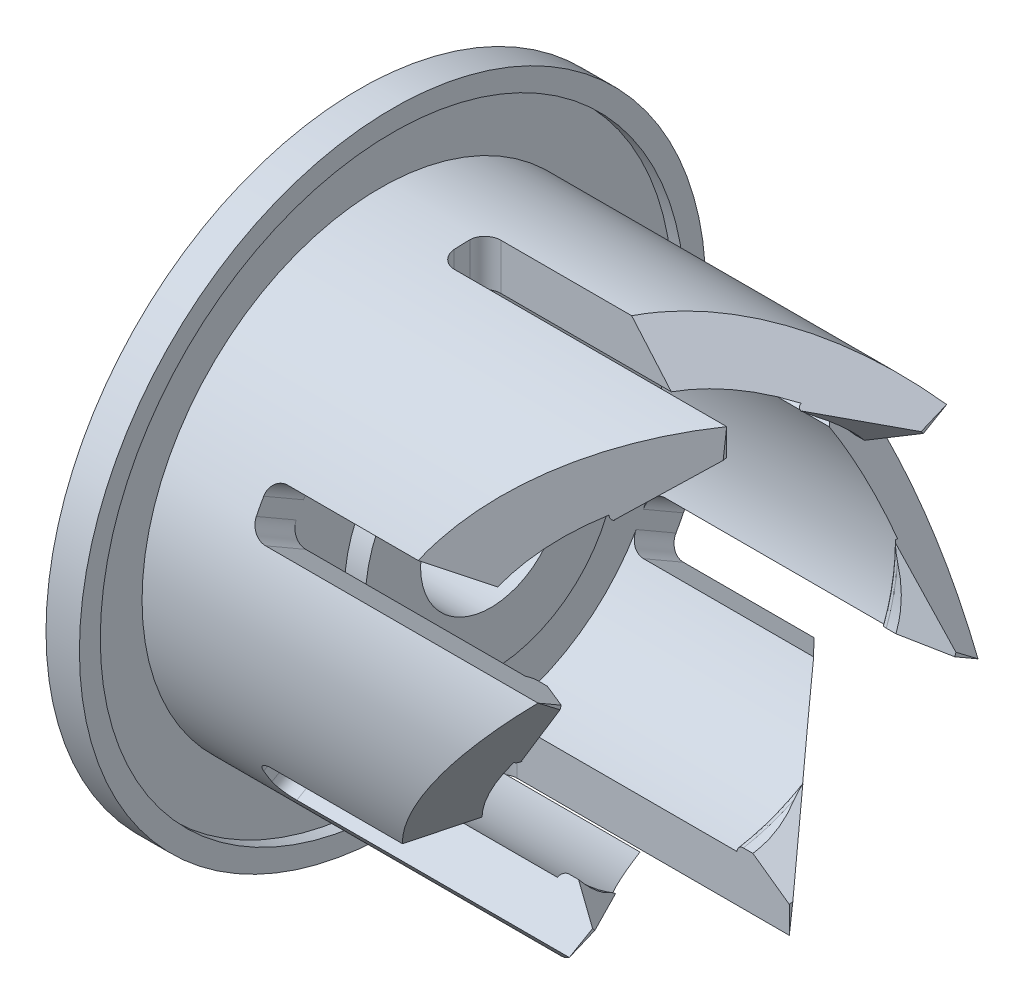
SolidWorks part; units mm, degrees
material "ABS"
ref_plane "Přední rovina" through (0, 0, 0) normal (0, 0, 1) x (1, 0, 0)
ref_plane "Horní rovina" through (0, 0, 0) normal (0, 1, 0) x (1, 0, 0)
ref_plane "Pravá rovina" through (0, 0, 0) normal (1, 0, 0) x (0, 0, -1)
sketch "Skica1" plane through (0, 0, 0) normal (0, 0, 1) x (1, 0, 0)
  line L0 (0, 0) -> (0, 5.15) construction
  line L4 (0, 3.36) -> (0, 15)
  line L5 (0, 15) -> (1.6, 15)
  line L6 (1.6, 15) -> (1.6, 14)
  line L7 (1.6, 14) -> (1, 14)
  line L8 (1, 14) -> (1, 11.4)
  line L9 (1, 11.4) -> (5.3, 11.4)
  line L10 (5.3, 11.4) -> (5.3, 6)
  line L11 (5.3, 6) -> (6.3, 6)
  line L12 (6.3, 6) -> (6.3, 0) construction
  line L14 (-2.607, 0) -> (10.0363, 0) construction
  line L16 (0, 3.36) -> (6.3, 3.36)
  line L17 (6.3, 3.36) -> (6.3, 6)
  dimension "D1" = 1
  dimension "D2" = 1.6
  dimension "D3" = 1
  dimension "D4" = 30
  dimension "D7" = 5.3
  dimension "D8" = 6.3
  dimension "D10" = 12
  dimension "D11" = 22.8
  dimension "D12" = 6.72
revolve "Rotovat1" add sketch "Skica1" angle 360 about L14
sketch "Skica2" plane through (5.3, 0, 0) normal (1, 0, 0) x (0, 0, -1)
  line L0 (0, 0) -> (0, 17.4116) construction
  line L1 (0, 0) -> (14.289, 8.2498) construction
  line L2 (9.0369, 6.9495) -> (7.1108, 5.8375)
  line L3 (0.75, 11.3753) -> (0.75, 9.1694)
  arc A0 (9.8727, 5.7) -> (0.75, 11.3753) centre (0, 0) ccw
  arc A1 (7.1108, 5.8375) -> (0.75, 9.1694) centre (0, 0) ccw
  circle A2 centre (0, 0) radius 11.4 construction
  circle M8 centre (0, 0) radius 11.4
  dimension "D1" = 2.2
  dimension "D3" = 1.5
  dimension "D2" = 60
  dimension "D4" = 1.5
extrude "Přidat vysunutím1" add sketch "Skica2" along normal blind 13.8 contours A1 L2 L3 M8 region at (5.3, 8.8858, -4.7069)
sketch "Skica pro odebrání" plane through (0, 0, -0.75) normal (0, 0, 1) x (1, 0, 0)
  line L0 (12.3, 11.3753) -> (14.2, 9.1694)
  line L1 (19.1, 11.3753) -> (5.3, 11.3753) construction
  line L2 (19.1, 9.1694) -> (5.3, 9.1694) construction
  dimension "D1" = 4.9
  dimension "D2" = 6.8
ref_plane "Rovina pro zkosení zubu" through (11.6607, 10.0435, 4.2044) normal (0.7309, 0.6295, 0.2635) x (0.1997, 0.172, -0.9646)
ref_plane "Rovina pro výstupek na zubu" through (16.6, 0, 0) normal (1, 0, 0) x (0, 0, -1)
sketch "Skica7" plane through (16.6, 0, 0) normal (1, 0, 0) x (0, 0, -1)
  line L0 (7.1108, 5.8375) -> (6.8474, 5.6854)
  line L1 (0.75, 9.1694) -> (0.75, 8.8683)
  arc A0 (7.1108, 5.8375) -> (0.75, 9.1694) centre (0, 0) ccw
  arc A1 (6.8474, 5.6854) -> (0.75, 8.8683) centre (0, 0) ccw
  dimension "D1" = 0.3
extrude "Přidat vysunutím2" add sketch "Skica7" along normal blind 2.5
sketch "Skica5" plane through (11.6607, 10.0435, 4.2044) normal (0.7309, 0.6295, 0.2635) x (0.1997, 0.172, -0.9646)
  line L0 (5.136, 0.5918) -> (5.136, -8.1865)
  line L1 (5.136, -8.1865) -> (13.7266, -8.1865)
  line L2 (13.7266, -8.1865) -> (13.7266, 0.5918)
  line L3 (13.7266, 0.5918) -> (5.136, 0.5918)
extrude "Odebrat vysunutím1" cut sketch "Skica5" along normal up to next
fillet "Zaoblit3" radius 0.3 1 edges at (16.6, 6.887, -5.6373)
fillet "Zaoblit2" radius 0.75 2 edges at (5.3, 6.3935, -8.0738) (5.3, 10.2723, -0.75)
sketch "Skica pro rovinu" plane through (19.1, 0, 0) normal (1, 0, 0) x (0, 0, -1)
  line L0 (6.8474, 5.6854) -> (6.6271, 5.9407)
ref_plane "Rovina pro zkosení" through (2.1028, -1.9619, 2.2738) normal (-0.5736, 0.5351, -0.6202) x (0, 0.7571, 0.6533)
sketch "Skica9" plane through (2.1028, -1.9619, 2.2738) normal (-0.5736, 0.5351, -0.6202) x (0, 0.7571, 0.6533)
  line L0 (1.3577, 25.1117) -> (-6.1069, 20.3992)
  line L1 (-6.1069, 20.3992) -> (-3.8641, 14.9295)
  line L2 (-3.8641, 14.9295) -> (5.9532, 20.1299)
  line L3 (5.9532, 20.1299) -> (1.3577, 25.1117)
extrude "Odebrat vysunutím2" cut sketch "Skica9" along normal blind 1
pattern_circular "Kruhové pole1" count 6 over 360 about axis through (6.3, 0, 0) along (-1, 0, 0) of "Odebrat vysunutím1", "Přidat vysunutím1", "Zaoblit2", "Zaoblit3", "Přidat vysunutím2", "Odebrat vysunutím2"
